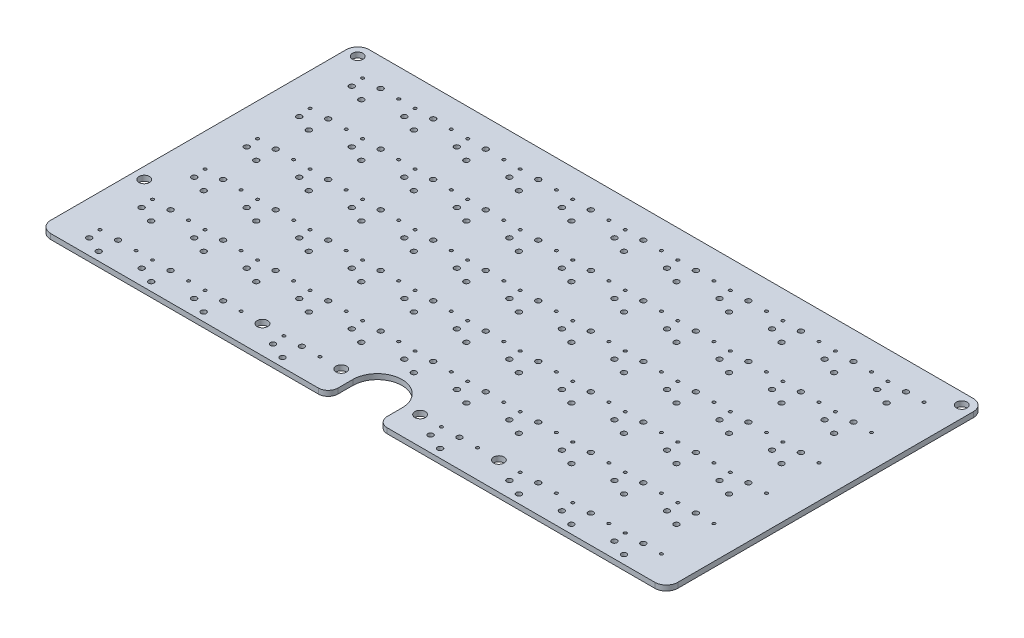
SolidWorks part; units mm, degrees
ref_plane "前视基准面" through (0, 0, 0) normal (0, 0, 1) x (1, 0, 0)
ref_plane "上视基准面" through (0, 0, 0) normal (0, 1, 0) x (1, 0, 0)
ref_plane "右视基准面" through (0, 0, 0) normal (1, 0, 0) x (0, 0, -1)
other "Configuration Table"
sketch "草图1" plane through (0, 0, 0) normal (0, 1, 0) x (1, 0, 0)
  line L0 (187.5, 94.5) -> (187.5, 99)
  line L1 (172.5, 94.5) -> (172.5, 99)
  line L2 (88, 91.5) -> (169.5, 91.5)
  line L3 (190.5, 91.5) -> (272, 91.5)
  line L4 (275.5, 95) -> (275.5, 185)
  line L5 (268.5, 188.5) -> (272, 188.5)
  line L6 (84.5, 185) -> (84.5, 95)
  line L7 (88, 188.5) -> (268.5, 188.5)
  circle A0 centre (187.5, 94.5) radius 0.05
  circle A1 centre (187.5, 99) radius 0.05
  circle A2 centre (172.5, 94.5) radius 0.05
  circle A3 centre (172.5, 99) radius 0.05
  circle A4 centre (88, 91.5) radius 0.05
  circle A5 centre (169.5, 91.5) radius 0.05
  circle A6 centre (190.5, 91.5) radius 0.05
  circle A7 centre (272, 91.5) radius 0.05
  circle A8 centre (275.5, 95) radius 0.05
  circle A9 centre (275.5, 185) radius 0.05
  circle A10 centre (268.5, 188.5) radius 0.05
  circle A11 centre (272, 188.5) radius 0.05
  circle A12 centre (84.5, 185) radius 0.05
  circle A13 centre (84.5, 95) radius 0.05
  circle A14 centre (88, 188.5) radius 0.05
  circle A15 centre (268.5, 188.5) radius 0.05
  arc A16 (180, 106.5) -> (172.5, 99) centre (180, 99) ccw
  circle A17 centre (172.5, 99) radius 0.05
  circle A18 centre (180, 106.5) radius 0.05
  arc A19 (187.5, 99) -> (180, 106.5) centre (180, 99) ccw
  circle A20 centre (180, 106.5) radius 0.05
  circle A21 centre (187.5, 99) radius 0.05
  arc A22 (187.5, 94.5) -> (190.5, 91.5) centre (190.5, 94.5) ccw
  circle A23 centre (190.5, 91.5) radius 0.05
  circle A24 centre (187.5, 94.5) radius 0.05
  arc A25 (169.5, 91.5) -> (172.5, 94.5) centre (169.5, 94.5) ccw
  circle A26 centre (172.5, 94.5) radius 0.05
  circle A27 centre (169.5, 91.5) radius 0.05
  arc A28 (272, 91.5) -> (275.5, 95) centre (272, 95) ccw
  circle A29 centre (275.5, 95) radius 0.05
  circle A30 centre (272, 91.5) radius 0.05
  arc A31 (275.5, 185) -> (272, 188.5) centre (272, 185) ccw
  circle A32 centre (272, 188.5) radius 0.05
  circle A33 centre (275.5, 185) radius 0.05
  arc A34 (88, 188.5) -> (84.5, 185) centre (88, 185) ccw
  circle A35 centre (84.5, 185) radius 0.05
  circle A36 centre (88, 188.5) radius 0.05
  arc A37 (84.5, 95) -> (88, 91.5) centre (88, 95) ccw
  circle A38 centre (88, 91.5) radius 0.05
  circle A39 centre (84.5, 95) radius 0.05
  circle A40 centre (246.6, 136.906) radius 0.1778
  circle A41 centre (170.8, 120.0531) radius 0.1778
  circle A42 centre (177.292, 121.92) radius 0.1778
  circle A43 centre (182.245, 121.666) radius 0.1778
  circle A44 centre (182.245, 119.866) radius 0.1778
  circle A45 centre (268.224, 96.797) radius 0.1778
  circle A46 centre (102.235, 106.1238) radius 0.1778
  circle A47 centre (116.905, 107.315) radius 0.1778
  circle A48 centre (132.905, 107.315) radius 0.1778
  circle A49 centre (156.845, 107.315) radius 0.1778
  circle A50 centre (97.536, 104.284) radius 0.1778
  circle A51 centre (113.5301, 104.284) radius 0.1778
  circle A52 centre (113.5301, 106.1238) radius 0.1778
  circle A53 centre (129.286, 104.284) radius 0.1778
  circle A54 centre (129.286, 106.1238) radius 0.1778
  circle A55 centre (153.5, 104.284) radius 0.1778
  circle A56 centre (153.5, 106.1238) radius 0.1778
  circle A57 centre (198.5, 106.2984) radius 0.1778
  circle A58 centre (225.679, 103.505) radius 0.1778
  circle A59 centre (201.5, 104.26) radius 0.1778
  circle A60 centre (241.5891, 103.759) radius 0.1778
  circle A61 centre (230, 106.6286) radius 0.1778
  circle A62 centre (206, 106.553) radius 0.1778
  circle A63 centre (246.1774, 106.6286) radius 0.1778
  circle A64 centre (260.731, 106.6286) radius 0.1778
  circle A65 centre (264.922, 102.87) radius 0.1778
  circle A66 centre (266.1079, 106.3419) radius 0.1778
  circle A67 centre (264.922, 108.077) radius 0.1778
  circle A68 centre (263.144, 108.077) radius 0.1778
  circle A69 centre (265.2682, 112.9682) radius 0.1778
  circle A70 centre (102.2, 119.42) radius 0.1778
  circle A71 centre (102.2, 121.316) radius 0.1778
  circle A72 centre (118.237, 119.42) radius 0.1778
  circle A73 centre (118.2, 121.316) radius 0.1778
  circle A74 centre (134.239, 119.42) radius 0.1778
  circle A75 centre (134.2, 121.316) radius 0.1778
  circle A76 centre (150.241, 119.42) radius 0.1778
  circle A77 centre (150.2, 121.316) radius 0.1778
  circle A78 centre (166.243, 119.42) radius 0.1778
  circle A79 centre (166.2, 121.316) radius 0.1778
  circle A80 centre (198.2, 119.42) radius 0.1778
  circle A81 centre (198.2, 121.316) radius 0.1778
  circle A82 centre (230.2, 119.42) radius 0.1778
  circle A83 centre (214.2, 119.42) radius 0.1778
  circle A84 centre (214.2, 121.316) radius 0.1778
  circle A85 centre (246.253, 119.6866) radius 0.1778
  circle A86 centre (246.2, 121.316) radius 0.1778
  circle A87 centre (230.2, 121.316) radius 0.1778
  circle A88 centre (262.2, 121.316) radius 0.1778
  circle A89 centre (99.969, 123.038) radius 0.1778
  circle A90 centre (115.969, 123.038) radius 0.1778
  circle A91 centre (131.969, 123.038) radius 0.1778
  circle A92 centre (147.969, 123.038) radius 0.1778
  circle A93 centre (163.969, 123.038) radius 0.1778
  circle A94 centre (179.969, 123.038) radius 0.1778
  circle A95 centre (195.969, 123.038) radius 0.1778
  circle A96 centre (211.969, 123.038) radius 0.1778
  circle A97 centre (227.969, 123.038) radius 0.1778
  circle A98 centre (243.969, 123.038) radius 0.1778
  circle A99 centre (259.969, 123.063) radius 0.1778
  circle A100 centre (257.429, 121.257) radius 0.1778
  circle A101 centre (241.5301, 121.257) radius 0.1778
  circle A102 centre (225.552, 121.316) radius 0.1778
  circle A103 centre (209.5, 121.316) radius 0.1778
  circle A104 centre (193.548, 121.285) radius 0.1778
  circle A105 centre (161.671, 121.316) radius 0.1778
  circle A106 centre (263.6404, 117.729) radius 0.1778
  circle A107 centre (257.6314, 118.618) radius 0.1778
  circle A108 centre (266.5897, 123.063) radius 0.1778
  circle A109 centre (231.6404, 124.46) radius 0.1778
  circle A110 centre (257.6314, 136.284) radius 0.1778
  circle A111 centre (257.556, 138.176) radius 0.1778
  circle A112 centre (241.5301, 137.922) radius 0.1778
  circle A113 centre (241.554, 136.144) radius 0.1778
  circle A114 centre (225.298, 136.284) radius 0.1778
  circle A115 centre (225.298, 138.2141) radius 0.1778
  circle A116 centre (209.55, 136.249) radius 0.1778
  circle A117 centre (209.55, 138.049) radius 0.1778
  circle A118 centre (195.126, 134.874) radius 0.1778
  circle A119 centre (179.126, 134.874) radius 0.1778
  circle A120 centre (163.126, 134.874) radius 0.1778
  circle A121 centre (147.126, 134.874) radius 0.1778
  circle A122 centre (131.126, 134.874) radius 0.1778
  circle A123 centre (115.126, 134.874) radius 0.1778
  circle A124 centre (99.126, 134.874) radius 0.1778
  circle A125 centre (116.956, 139.192) radius 0.1778
  circle A126 centre (132.956, 139.192) radius 0.1778
  circle A127 centre (148.956, 139.192) radius 0.1778
  circle A128 centre (164.956, 139.192) radius 0.1778
  circle A129 centre (180.956, 139.192) radius 0.1778
  circle A130 centre (196.956, 139.192) radius 0.1778
  circle A131 centre (212.956, 139.192) radius 0.1778
  circle A132 centre (228.956, 139.192) radius 0.1778
  circle A133 centre (244.956, 139.192) radius 0.1778
  circle A134 centre (260.956, 139.192) radius 0.1778
  circle A135 centre (100.965, 139.192) radius 0.1778
  circle A136 centre (268.478, 138.938) radius 0.1778
  circle A137 centre (268.5, 155.067) radius 0.1778
  circle A138 centre (182.247, 152.216) radius 0.1778
  circle A139 centre (166.247, 152.216) radius 0.1778
  circle A140 centre (150.247, 152.216) radius 0.1778
  circle A141 centre (134.247, 152.216) radius 0.1778
  circle A142 centre (118.2165, 152.216) radius 0.1778
  circle A143 centre (102.247, 152.216) radius 0.1778
  circle A144 centre (102.247, 154.0137) radius 0.1778
  circle A145 centre (118.247, 154.0137) radius 0.1778
  circle A146 centre (134.247, 154.0137) radius 0.1778
  circle A147 centre (150.247, 154.0137) radius 0.1778
  circle A148 centre (166.247, 154.0137) radius 0.1778
  circle A149 centre (182.247, 154.0137) radius 0.1778
  circle A150 centre (198.247, 154.0137) radius 0.1778
  circle A151 centre (214.249, 154.0137) radius 0.1778
  circle A152 centre (230.194, 154.0137) radius 0.1778
  circle A153 centre (246.253, 154.0137) radius 0.1778
  circle A154 centre (230.251, 152.273) radius 0.1778
  circle A155 centre (198.247, 152.273) radius 0.1778
  circle A156 centre (193.576, 153.278) radius 0.1778
  circle A157 centre (177.576, 153.278) radius 0.1778
  circle A158 centre (116, 155.067) radius 0.1778
  circle A159 centre (132, 155.067) radius 0.1778
  circle A160 centre (148, 155.067) radius 0.1778
  circle A161 centre (164, 155.067) radius 0.1778
  circle A162 centre (180, 155.067) radius 0.1778
  circle A163 centre (196, 155.067) radius 0.1778
  circle A164 centre (212, 155.067) radius 0.1778
  circle A165 centre (228, 155.067) radius 0.1778
  circle A166 centre (244, 155.067) radius 0.1778
  circle A167 centre (257.5301, 154.051) radius 0.1778
  circle A168 centre (260, 155.067) radius 0.1778
  circle A169 centre (102, 170.942) radius 0.1778
  circle A170 centre (102.362, 168.284) radius 0.1778
  circle A171 centre (97.542, 168.402) radius 0.1778
  circle A172 centre (113.542, 168.402) radius 0.1778
  circle A173 centre (113.411, 169.926) radius 0.1778
  circle A174 centre (129.542, 168.402) radius 0.1778
  circle A175 centre (129.54, 169.926) radius 0.1778
  circle A176 centre (118.2165, 168.284) radius 0.1778
  circle A177 centre (150.241, 168.402) radius 0.1778
  circle A178 centre (134.239, 168.284) radius 0.1778
  circle A179 centre (145.542, 168.402) radius 0.1778
  circle A180 centre (145.5301, 169.926) radius 0.1778
  circle A181 centre (161.417, 168.402) radius 0.1778
  circle A182 centre (161.417, 169.926) radius 0.1778
  circle A183 centre (166.243, 168.2844) radius 0.1778
  circle A184 centre (177.546, 168.402) radius 0.1778
  circle A185 centre (177.5301, 169.926) radius 0.1778
  circle A186 centre (182.245, 168.284) radius 0.1778
  circle A187 centre (193.548, 168.284) radius 0.1778
  circle A188 centre (193.548, 169.926) radius 0.1778
  circle A189 centre (198.247, 168.284) radius 0.1778
  circle A190 centre (209.55, 168.284) radius 0.1778
  circle A191 centre (209.5301, 169.926) radius 0.1778
  circle A192 centre (214.249, 168.284) radius 0.1778
  circle A193 centre (230.251, 168.284) radius 0.1778
  circle A194 centre (225.576, 168.3344) radius 0.1778
  circle A195 centre (225.552, 169.926) radius 0.1778
  circle A196 centre (241.554, 168.3344) radius 0.1778
  circle A197 centre (241.5301, 169.926) radius 0.1778
  circle A198 centre (246.253, 168.284) radius 0.1778
  circle A199 centre (257.5301, 168.284) radius 0.1778
  circle A200 centre (257.5301, 169.926) radius 0.1778
  circle A201 centre (262.255, 153.416) radius 0.1778
  circle A202 centre (99.06, 150.876) radius 0.1778
  circle A203 centre (247.637, 156.337) radius 0.1778
  circle A204 centre (254.762, 172.974) radius 0.1778
  circle A205 centre (102.362, 184.873) radius 0.1778
  circle A206 centre (100.9291, 182.8787) radius 0.1778
  circle A207 centre (118.4302, 184.873) radius 0.1778
  circle A208 centre (116.967, 182.8787) radius 0.1778
  circle A209 centre (134.239, 184.873) radius 0.1778
  circle A210 centre (132.969, 182.88) radius 0.1778
  circle A211 centre (150.241, 184.873) radius 0.1778
  circle A212 centre (148.905, 182.88) radius 0.1778
  circle A213 centre (166.37, 184.873) radius 0.1778
  circle A214 centre (164.895, 182.88) radius 0.1778
  circle A215 centre (182.372, 184.912) radius 0.1778
  circle A216 centre (180.975, 182.88) radius 0.1778
  circle A217 centre (198.374, 184.873) radius 0.1778
  circle A218 centre (196.925, 182.88) radius 0.1778
  circle A219 centre (214.376, 184.873) radius 0.1778
  circle A220 centre (212.979, 182.88) radius 0.1778
  circle A221 centre (230.251, 184.873) radius 0.1778
  circle A222 centre (246.253, 184.873) radius 0.1778
  circle A223 centre (262.382, 184.873) radius 0.1778
  circle A224 centre (244.983, 182.88) radius 0.1778
  circle A225 centre (228.925, 182.9495) radius 0.1778
  circle A226 centre (256.929, 183.428) radius 0.1778
  circle A227 centre (240.927, 183.42) radius 0.1778
  circle A228 centre (224.925, 183.428) radius 0.1778
  circle A229 centre (208.923, 183.428) radius 0.1778
  circle A230 centre (192.921, 183.428) radius 0.1778
  circle A231 centre (176.919, 183.428) radius 0.1778
  circle A232 centre (160.917, 183.428) radius 0.1778
  circle A233 centre (144.915, 183.42) radius 0.1778
  circle A234 centre (128.667, 183.428) radius 0.1778
  circle A235 centre (112.649, 183.428) radius 0.1778
  circle A236 centre (96.393, 185) radius 0.1778
  circle A237 centre (99.072, 182.8787) radius 0.1778
  circle A238 centre (115.095, 182.935) radius 0.1778
  circle A239 centre (131.075, 182.925) radius 0.1778
  circle A240 centre (147.185, 182.88) radius 0.1778
  circle A241 centre (163.068, 182.88) radius 0.1778
  circle A242 centre (179.07, 182.88) radius 0.1778
  circle A243 centre (195.072, 182.938) radius 0.1778
  circle A244 centre (211.095, 182.938) radius 0.1778
  circle A245 centre (227.072, 182.938) radius 0.1778
  circle A246 centre (243.072, 182.938) radius 0.1778
  circle A247 centre (259.185, 182.938) radius 0.1778
  circle A248 centre (164.895, 170.942) radius 0.1778
  circle A249 centre (148.905, 170.942) radius 0.1778
  circle A250 centre (196.885, 170.942) radius 0.1778
  circle A251 centre (212.885, 170.942) radius 0.1778
  circle A252 centre (228.885, 170.942) radius 0.1778
  circle A253 centre (244.885, 170.942) radius 0.1778
  circle A254 centre (260.885, 170.942) radius 0.1778
  circle A255 centre (268.478, 170.942) radius 0.1778
  circle A256 centre (180.885, 170.942) radius 0.1778
  circle A257 centre (132.885, 170.942) radius 0.1778
  circle A258 centre (116.885, 170.942) radius 0.1778
  circle A259 centre (271.018, 166.37) radius 0.1778
  circle A260 centre (170.561, 167.767) radius 0.1778
  circle A261 centre (106.8, 185.666) radius 0.1778
  circle A262 centre (122.8, 185.666) radius 0.1778
  circle A263 centre (255.524, 182) radius 0.1778
  circle A264 centre (249.5, 107.8945) radius 0.1778
  circle A265 centre (257.556, 104.297) radius 0.1778
  circle A266 centre (272.415, 95.377) radius 0.1778
  circle A267 centre (271.4106, 97.1434) radius 0.1778
  circle A268 centre (271.018, 107.696) radius 0.1778
  circle A269 centre (270.2444, 180.2014) radius 0.1778
  circle A270 centre (273.558, 180.213) radius 0.1778
  circle A271 centre (268.224, 100.076) radius 0.1778
  circle A272 centre (254.5, 104.297) radius 0.1778
  circle A273 centre (270.002, 100) radius 0.1778
  circle A274 centre (236.093, 104.284) radius 0.1778
  circle A275 centre (252.1274, 104.284) radius 0.1778
  circle A276 centre (262.2, 104.284) radius 0.1778
  circle A277 centre (236.347, 142.113) radius 0.1778
  circle A278 centre (257.556, 185.293) radius 0.1778
  circle A279 centre (241.554, 185.293) radius 0.1778
  circle A280 centre (225.552, 185.293) radius 0.1778
  circle A281 centre (209.55, 185.293) radius 0.1778
  circle A282 centre (193.548, 185.293) radius 0.1778
  circle A283 centre (177.576, 185.316) radius 0.1778
  circle A284 centre (161.671, 185.316) radius 0.1778
  circle A285 centre (145.63, 185.316) radius 0.1778
  circle A286 centre (129.54, 185.316) radius 0.1778
  circle A287 centre (113.411, 185.293) radius 0.1778
  circle A288 centre (246.253, 152.273) radius 0.1778
  circle A289 centre (241.554, 153.316) radius 0.1778
  circle A290 centre (225.552, 153.316) radius 0.1778
  circle A291 centre (214.249, 152.273) radius 0.1778
  circle A292 centre (209.55, 153.316) radius 0.1778
  circle A293 centre (161.671, 153.316) radius 0.1778
  circle A294 centre (145.63, 153.316) radius 0.1778
  circle A295 centre (129.54, 153.316) radius 0.1778
  circle A296 centre (113.665, 153.316) radius 0.1778
  circle A297 centre (102.489, 136.271) radius 0.1778
  circle A298 centre (113.665, 137.414) radius 0.1778
  circle A299 centre (118.237, 136.284) radius 0.1778
  circle A300 centre (129.54, 137.414) radius 0.1778
  circle A301 centre (134.239, 136.284) radius 0.1778
  circle A302 centre (145.6, 137.414) radius 0.1778
  circle A303 centre (150.241, 136.284) radius 0.1778
  circle A304 centre (161.671, 137.384) radius 0.1778
  circle A305 centre (166.243, 136.284) radius 0.1778
  circle A306 centre (177.546, 137.414) radius 0.1778
  circle A307 centre (182.245, 136.284) radius 0.1778
  circle A308 centre (193.802, 137.414) radius 0.1778
  circle A309 centre (198.447, 136.284) radius 0.1778
  circle A310 centre (214.249, 136.284) radius 0.1778
  circle A311 centre (230.505, 136.284) radius 0.1778
  circle A312 centre (145.6, 121.316) radius 0.1778
  circle A313 centre (129.54, 121.316) radius 0.1778
  circle A314 centre (113.665, 121.316) radius 0.1778
  circle A315 centre (102.235, 104.26) radius 0.1778
  circle A316 centre (118.237, 104.26) radius 0.1778
  circle A317 centre (146.818, 103.505) radius 0.1778
  circle A318 centre (134.239, 104.284) radius 0.1778
  circle A319 centre (218.8, 103.251) radius 0.1778
  circle A320 centre (225.552, 105.384) radius 0.1778
  circle A321 centre (206, 104.26) radius 0.1778
  circle A322 centre (241.554, 105.384) radius 0.1778
  circle A323 centre (230, 104.26) radius 0.1778
  circle A324 centre (246.253, 104.26) radius 0.1778
  circle A325 centre (250.8, 119.42) radius 0.1778
  circle A326 centre (250.8, 135.42) radius 0.1778
  circle A327 centre (250.8, 151.42) radius 0.1778
  circle A328 centre (250.8, 167.42) radius 0.1778
  circle A329 centre (250.8, 183.428) radius 0.1778
  circle A330 centre (234.8, 119.42) radius 0.1778
  circle A331 centre (234.8, 135.42) radius 0.1778
  circle A332 centre (234.8, 151.42) radius 0.1778
  circle A333 centre (234.8, 167.42) radius 0.1778
  circle A334 centre (234.8, 183.428) radius 0.1778
  circle A335 centre (218.8, 119.42) radius 0.1778
  circle A336 centre (218.8, 135.42) radius 0.1778
  circle A337 centre (218.8, 151.42) radius 0.1778
  circle A338 centre (218.8, 167.42) radius 0.1778
  circle A339 centre (218.8, 183.428) radius 0.1778
  circle A340 centre (202.8, 119.42) radius 0.1778
  circle A341 centre (202.8, 135.42) radius 0.1778
  circle A342 centre (202.8, 151.42) radius 0.1778
  circle A343 centre (202.8, 167.42) radius 0.1778
  circle A344 centre (202.8, 183.428) radius 0.1778
  circle A345 centre (186.8, 119.42) radius 0.1778
  circle A346 centre (186.8, 135.42) radius 0.1778
  circle A347 centre (186.8, 151.42) radius 0.1778
  circle A348 centre (186.8, 167.42) radius 0.1778
  circle A349 centre (186.8, 183.428) radius 0.1778
  circle A350 centre (170.8, 135.42) radius 0.1778
  circle A351 centre (170.8, 151.42) radius 0.1778
  circle A352 centre (170.561, 183.428) radius 0.1778
  circle A353 centre (154.8, 119.42) radius 0.1778
  circle A354 centre (154.8, 135.42) radius 0.1778
  circle A355 centre (154.8, 151.42) radius 0.1778
  circle A356 centre (154.8, 167.42) radius 0.1778
  circle A357 centre (154.8, 183.428) radius 0.1778
  circle A358 centre (138.8, 119.42) radius 0.1778
  circle A359 centre (138.8, 135.42) radius 0.1778
  circle A360 centre (138.8, 151.42) radius 0.1778
  circle A361 centre (138.8, 167.42) radius 0.1778
  circle A362 centre (138.8, 183.428) radius 0.1778
  circle A363 centre (122.8, 102.42) radius 0.1778
  circle A364 centre (122.8, 119.42) radius 0.1778
  circle A365 centre (122.8, 135.42) radius 0.1778
  circle A366 centre (122.8, 151.42) radius 0.1778
  circle A367 centre (122.8, 167.42) radius 0.1778
  circle A368 centre (122.8, 183.428) radius 0.1778
  circle A369 centre (106.8, 102.512) radius 0.1778
  circle A370 centre (106.8, 119.42) radius 0.1778
  circle A371 centre (106.8, 135.42) radius 0.1778
  circle A372 centre (106.8, 151.42) radius 0.1778
  circle A373 centre (106.8, 167.42) radius 0.1778
  circle A374 centre (106.8, 183.428) radius 0.1778
  circle A375 centre (93.472, 183.428) radius 0.1778
  circle A376 centre (92.075, 168.91) radius 0.1778
  circle A377 centre (92.075, 153.035) radius 0.1778
  circle A378 centre (92.075, 136.906) radius 0.1778
  circle A379 centre (88, 120) radius 0.8
  circle A380 centre (216, 100) radius 0.8
  circle A381 centre (144, 100) radius 0.8
  circle A382 centre (192, 100) radius 0.8
  circle A383 centre (168, 100) radius 0.8
  circle A384 centre (272, 185) radius 0.8
  circle A385 centre (88, 185) radius 0.8
  circle A386 centre (239, 176.2) radius 0.8
  circle A387 centre (244, 174.1) radius 0.8
  circle A388 centre (244, 180) radius 0.8
  circle A389 centre (249.5, 180) radius 0.45
  circle A390 centre (238.5, 180) radius 0.45
  circle A391 centre (222.5, 180) radius 0.45
  circle A392 centre (233.5, 180) radius 0.45
  circle A393 centre (228, 180) radius 0.8
  circle A394 centre (228, 174.1) radius 0.8
  circle A395 centre (223, 176.2) radius 0.8
  circle A396 centre (207, 176.2) radius 0.8
  circle A397 centre (212, 174.1) radius 0.8
  circle A398 centre (212, 180) radius 0.8
  circle A399 centre (217.5, 180) radius 0.45
  circle A400 centre (206.5, 180) radius 0.45
  circle A401 centre (190.5, 180) radius 0.45
  circle A402 centre (201.5, 180) radius 0.45
  circle A403 centre (196, 180) radius 0.8
  circle A404 centre (196, 174.1) radius 0.8
  circle A405 centre (191, 176.2) radius 0.8
  circle A406 centre (175, 176.2) radius 0.8
  circle A407 centre (180, 174.1) radius 0.8
  circle A408 centre (180, 180) radius 0.8
  circle A409 centre (185.5, 180) radius 0.45
  circle A410 centre (174.5, 180) radius 0.45
  circle A411 centre (158.5, 180) radius 0.45
  circle A412 centre (169.5, 180) radius 0.45
  circle A413 centre (164, 180) radius 0.8
  circle A414 centre (164, 174.1) radius 0.8
  circle A415 centre (159, 176.2) radius 0.8
  circle A416 centre (143, 176.2) radius 0.8
  circle A417 centre (148, 174.1) radius 0.8
  circle A418 centre (148, 180) radius 0.8
  circle A419 centre (153.5, 180) radius 0.45
  circle A420 centre (142.5, 180) radius 0.45
  circle A421 centre (126.5, 180) radius 0.45
  circle A422 centre (137.5, 180) radius 0.45
  circle A423 centre (132, 180) radius 0.8
  circle A424 centre (132, 174.1) radius 0.8
  circle A425 centre (127, 176.2) radius 0.8
  circle A426 centre (111, 176.2) radius 0.8
  circle A427 centre (116, 174.1) radius 0.8
  circle A428 centre (116, 180) radius 0.8
  circle A429 centre (121.5, 180) radius 0.45
  circle A430 centre (110.5, 180) radius 0.45
  circle A431 centre (94.5, 180) radius 0.45
  circle A432 centre (105.5, 180) radius 0.45
  circle A433 centre (100, 180) radius 0.8
  circle A434 centre (100, 174.1) radius 0.8
  circle A435 centre (95, 176.2) radius 0.8
  circle A436 centre (239, 160.2) radius 0.8
  circle A437 centre (244, 158.1) radius 0.8
  circle A438 centre (244, 164) radius 0.8
  circle A439 centre (249.5, 164) radius 0.45
  circle A440 centre (238.5, 164) radius 0.45
  circle A441 centre (222.5, 164) radius 0.45
  circle A442 centre (233.5, 164) radius 0.45
  circle A443 centre (228, 164) radius 0.8
  circle A444 centre (228, 158.1) radius 0.8
  circle A445 centre (223, 160.2) radius 0.8
  circle A446 centre (207, 160.2) radius 0.8
  circle A447 centre (212, 158.1) radius 0.8
  circle A448 centre (212, 164) radius 0.8
  circle A449 centre (217.5, 164) radius 0.45
  circle A450 centre (206.5, 164) radius 0.45
  circle A451 centre (190.5, 164) radius 0.45
  circle A452 centre (201.5, 164) radius 0.45
  circle A453 centre (196, 164) radius 0.8
  circle A454 centre (196, 158.1) radius 0.8
  circle A455 centre (191, 160.2) radius 0.8
  circle A456 centre (175, 160.2) radius 0.8
  circle A457 centre (180, 158.1) radius 0.8
  circle A458 centre (180, 164) radius 0.8
  circle A459 centre (185.5, 164) radius 0.45
  circle A460 centre (174.5, 164) radius 0.45
  circle A461 centre (158.5, 164) radius 0.45
  circle A462 centre (169.5, 164) radius 0.45
  circle A463 centre (164, 164) radius 0.8
  circle A464 centre (164, 158.1) radius 0.8
  circle A465 centre (159, 160.2) radius 0.8
  circle A466 centre (143, 160.2) radius 0.8
  circle A467 centre (148, 158.1) radius 0.8
  circle A468 centre (148, 164) radius 0.8
  circle A469 centre (153.5, 164) radius 0.45
  circle A470 centre (142.5, 164) radius 0.45
  circle A471 centre (126.5, 164) radius 0.45
  circle A472 centre (137.5, 164) radius 0.45
  circle A473 centre (132, 164) radius 0.8
  circle A474 centre (132, 158.1) radius 0.8
  circle A475 centre (127, 160.2) radius 0.8
  circle A476 centre (111, 160.2) radius 0.8
  circle A477 centre (116, 158.1) radius 0.8
  circle A478 centre (116, 164) radius 0.8
  circle A479 centre (121.5, 164) radius 0.45
  circle A480 centre (110.5, 164) radius 0.45
  circle A481 centre (94.5, 164) radius 0.45
  circle A482 centre (105.5, 164) radius 0.45
  circle A483 centre (100, 164) radius 0.8
  circle A484 centre (100, 158.1) radius 0.8
  circle A485 centre (95, 160.2) radius 0.8
  circle A486 centre (239, 144.2) radius 0.8
  circle A487 centre (244, 142.1) radius 0.8
  circle A488 centre (244, 148) radius 0.8
  circle A489 centre (249.5, 148) radius 0.45
  circle A490 centre (238.5, 148) radius 0.45
  circle A491 centre (222.5, 148) radius 0.45
  circle A492 centre (233.5, 148) radius 0.45
  circle A493 centre (228, 148) radius 0.8
  circle A494 centre (228, 142.1) radius 0.8
  circle A495 centre (223, 144.2) radius 0.8
  circle A496 centre (207, 144.2) radius 0.8
  circle A497 centre (212, 142.1) radius 0.8
  circle A498 centre (212, 148) radius 0.8
  circle A499 centre (217.5, 148) radius 0.45
  circle A500 centre (206.5, 148) radius 0.45
  circle A501 centre (190.5, 148) radius 0.45
  circle A502 centre (201.5, 148) radius 0.45
  circle A503 centre (196, 148) radius 0.8
  circle A504 centre (196, 142.1) radius 0.8
  circle A505 centre (191, 144.2) radius 0.8
  circle A506 centre (175, 144.2) radius 0.8
  circle A507 centre (180, 142.1) radius 0.8
  circle A508 centre (180, 148) radius 0.8
  circle A509 centre (185.5, 148) radius 0.45
  circle A510 centre (174.5, 148) radius 0.45
  circle A511 centre (158.5, 148) radius 0.45
  circle A512 centre (169.5, 148) radius 0.45
  circle A513 centre (164, 148) radius 0.8
  circle A514 centre (164, 142.1) radius 0.8
  circle A515 centre (159, 144.2) radius 0.8
  circle A516 centre (143, 144.2) radius 0.8
  circle A517 centre (148, 142.1) radius 0.8
  circle A518 centre (148, 148) radius 0.8
  circle A519 centre (153.5, 148) radius 0.45
  circle A520 centre (142.5, 148) radius 0.45
  circle A521 centre (126.5, 148) radius 0.45
  circle A522 centre (137.5, 148) radius 0.45
  circle A523 centre (132, 148) radius 0.8
  circle A524 centre (132, 142.1) radius 0.8
  circle A525 centre (127, 144.2) radius 0.8
  circle A526 centre (111, 144.2) radius 0.8
  circle A527 centre (116, 142.1) radius 0.8
  circle A528 centre (116, 148) radius 0.8
  circle A529 centre (121.5, 148) radius 0.45
  circle A530 centre (110.5, 148) radius 0.45
  circle A531 centre (94.5, 148) radius 0.45
  circle A532 centre (105.5, 148) radius 0.45
  circle A533 centre (100, 148) radius 0.8
  circle A534 centre (100, 142.1) radius 0.8
  circle A535 centre (95, 144.2) radius 0.8
  circle A536 centre (239, 128.2) radius 0.8
  circle A537 centre (244, 126.1) radius 0.8
  circle A538 centre (244, 132) radius 0.8
  circle A539 centre (249.5, 132) radius 0.45
  circle A540 centre (238.5, 132) radius 0.45
  circle A541 centre (222.5, 132) radius 0.45
  circle A542 centre (233.5, 132) radius 0.45
  circle A543 centre (228, 132) radius 0.8
  circle A544 centre (228, 126.1) radius 0.8
  circle A545 centre (223, 128.2) radius 0.8
  circle A546 centre (207, 128.2) radius 0.8
  circle A547 centre (212, 126.1) radius 0.8
  circle A548 centre (212, 132) radius 0.8
  circle A549 centre (217.5, 132) radius 0.45
  circle A550 centre (206.5, 132) radius 0.45
  circle A551 centre (190.5, 132) radius 0.45
  circle A552 centre (201.5, 132) radius 0.45
  circle A553 centre (196, 132) radius 0.8
  circle A554 centre (196, 126.1) radius 0.8
  circle A555 centre (191, 128.2) radius 0.8
  circle A556 centre (175, 128.2) radius 0.8
  circle A557 centre (180, 126.1) radius 0.8
  circle A558 centre (180, 132) radius 0.8
  circle A559 centre (185.5, 132) radius 0.45
  circle A560 centre (174.5, 132) radius 0.45
  circle A561 centre (158.5, 132) radius 0.45
  circle A562 centre (169.5, 132) radius 0.45
  circle A563 centre (164, 132) radius 0.8
  circle A564 centre (164, 126.1) radius 0.8
  circle A565 centre (159, 128.2) radius 0.8
  circle A566 centre (143, 128.2) radius 0.8
  circle A567 centre (148, 126.1) radius 0.8
  circle A568 centre (148, 132) radius 0.8
  circle A569 centre (153.5, 132) radius 0.45
  circle A570 centre (142.5, 132) radius 0.45
  circle A571 centre (126.5, 132) radius 0.45
  circle A572 centre (137.5, 132) radius 0.45
  circle A573 centre (132, 132) radius 0.8
  circle A574 centre (132, 126.1) radius 0.8
  circle A575 centre (127, 128.2) radius 0.8
  circle A576 centre (111, 128.2) radius 0.8
  circle A577 centre (116, 126.1) radius 0.8
  circle A578 centre (116, 132) radius 0.8
  circle A579 centre (121.5, 132) radius 0.45
  circle A580 centre (110.5, 132) radius 0.45
  circle A581 centre (94.5, 132) radius 0.45
  circle A582 centre (105.5, 132) radius 0.45
  circle A583 centre (100, 132) radius 0.8
  circle A584 centre (100, 126.1) radius 0.8
  circle A585 centre (95, 128.2) radius 0.8
  circle A586 centre (239, 112.2) radius 0.8
  circle A587 centre (244, 110.1) radius 0.8
  circle A588 centre (244, 116) radius 0.8
  circle A589 centre (249.5, 116) radius 0.45
  circle A590 centre (238.5, 116) radius 0.45
  circle A591 centre (222.5, 116) radius 0.45
  circle A592 centre (233.5, 116) radius 0.45
  circle A593 centre (228, 116) radius 0.8
  circle A594 centre (228, 110.1) radius 0.8
  circle A595 centre (223, 112.2) radius 0.8
  circle A596 centre (207, 112.2) radius 0.8
  circle A597 centre (212, 110.1) radius 0.8
  circle A598 centre (212, 116) radius 0.8
  circle A599 centre (217.5, 116) radius 0.45
  circle A600 centre (206.5, 116) radius 0.45
  circle A601 centre (190.5, 116) radius 0.45
  circle A602 centre (201.5, 116) radius 0.45
  circle A603 centre (196, 116) radius 0.8
  circle A604 centre (196, 110.1) radius 0.8
  circle A605 centre (191, 112.2) radius 0.8
  circle A606 centre (175, 112.2) radius 0.8
  circle A607 centre (180, 110.1) radius 0.8
  circle A608 centre (180, 116) radius 0.8
  circle A609 centre (185.5, 116) radius 0.45
  circle A610 centre (174.5, 116) radius 0.45
  circle A611 centre (158.5, 116) radius 0.45
  circle A612 centre (169.5, 116) radius 0.45
  circle A613 centre (164, 116) radius 0.8
  circle A614 centre (164, 110.1) radius 0.8
  circle A615 centre (159, 112.2) radius 0.8
  circle A616 centre (143, 112.2) radius 0.8
  circle A617 centre (148, 110.1) radius 0.8
  circle A618 centre (148, 116) radius 0.8
  circle A619 centre (153.5, 116) radius 0.45
  circle A620 centre (142.5, 116) radius 0.45
  circle A621 centre (126.5, 116) radius 0.45
  circle A622 centre (137.5, 116) radius 0.45
  circle A623 centre (132, 116) radius 0.8
  circle A624 centre (132, 110.1) radius 0.8
  circle A625 centre (127, 112.2) radius 0.8
  circle A626 centre (111, 112.2) radius 0.8
  circle A627 centre (116, 110.1) radius 0.8
  circle A628 centre (116, 116) radius 0.8
  circle A629 centre (121.5, 116) radius 0.45
  circle A630 centre (110.5, 116) radius 0.45
  circle A631 centre (94.5, 116) radius 0.45
  circle A632 centre (105.5, 116) radius 0.45
  circle A633 centre (100, 116) radius 0.8
  circle A634 centre (100, 110.1) radius 0.8
  circle A635 centre (95, 112.2) radius 0.8
  circle A636 centre (239, 96.2) radius 0.8
  circle A637 centre (244, 94.1) radius 0.8
  circle A638 centre (244, 100) radius 0.8
  circle A639 centre (249.5, 100) radius 0.45
  circle A640 centre (238.5, 100) radius 0.45
  circle A641 centre (222.5, 100) radius 0.45
  circle A642 centre (233.5, 100) radius 0.45
  circle A643 centre (228, 100) radius 0.8
  circle A644 centre (228, 94.1) radius 0.8
  circle A645 centre (223, 96.2) radius 0.8
  circle A646 centre (199, 96.2) radius 0.8
  circle A647 centre (204, 94.1) radius 0.8
  circle A648 centre (204, 100) radius 0.8
  circle A649 centre (209.5, 100) radius 0.45
  circle A650 centre (198.5, 100) radius 0.45
  circle A651 centre (254.5, 180) radius 0.45
  circle A652 centre (265.5, 180) radius 0.45
  circle A653 centre (260, 180) radius 0.8
  circle A654 centre (260, 174.1) radius 0.8
  circle A655 centre (255, 176.2) radius 0.8
  circle A656 centre (255, 160.2) radius 0.8
  circle A657 centre (260, 158.1) radius 0.8
  circle A658 centre (260, 164) radius 0.8
  circle A659 centre (265.5, 164) radius 0.45
  circle A660 centre (254.5, 164) radius 0.45
  circle A661 centre (150.5, 100) radius 0.45
  circle A662 centre (161.5, 100) radius 0.45
  circle A663 centre (156, 100) radius 0.8
  circle A664 centre (156, 94.1) radius 0.8
  circle A665 centre (151, 96.2) radius 0.8
  circle A666 centre (255, 144.2) radius 0.8
  circle A667 centre (260, 142.1) radius 0.8
  circle A668 centre (260, 148) radius 0.8
  circle A669 centre (265.5, 148) radius 0.45
  circle A670 centre (254.5, 148) radius 0.45
  circle A671 centre (126.5, 100) radius 0.45
  circle A672 centre (137.5, 100) radius 0.45
  circle A673 centre (132, 100) radius 0.8
  circle A674 centre (132, 94.1) radius 0.8
  circle A675 centre (127, 96.2) radius 0.8
  circle A676 centre (255, 128.2) radius 0.8
  circle A677 centre (260, 126.1) radius 0.8
  circle A678 centre (260, 132) radius 0.8
  circle A679 centre (265.5, 132) radius 0.45
  circle A680 centre (254.5, 132) radius 0.45
  circle A681 centre (110.5, 100) radius 0.45
  circle A682 centre (121.5, 100) radius 0.45
  circle A683 centre (116, 100) radius 0.8
  circle A684 centre (116, 94.1) radius 0.8
  circle A685 centre (111, 96.2) radius 0.8
  circle A686 centre (255, 112.2) radius 0.8
  circle A687 centre (260, 110.1) radius 0.8
  circle A688 centre (260, 116) radius 0.8
  circle A689 centre (265.5, 116) radius 0.45
  circle A690 centre (254.5, 116) radius 0.45
  circle A691 centre (94.5, 100) radius 0.45
  circle A692 centre (105.5, 100) radius 0.45
  circle A693 centre (100, 100) radius 0.8
  circle A694 centre (100, 94.1) radius 0.8
  circle A695 centre (95, 96.2) radius 0.8
  circle A696 centre (255, 96.2) radius 0.8
  circle A697 centre (260, 94.1) radius 0.8
  circle A698 centre (260, 100) radius 0.8
  circle A699 centre (265.5, 100) radius 0.45
  circle A700 centre (254.5, 100) radius 0.45
sketch "草图2" plane through (0, 0, 0) normal (0, 1, 0) x (1, 0, 0)
  line L8 (187.5, 99) -> (187.5, 94.5)
  line L9 (190.5, 91.5) -> (272, 91.5)
  line L10 (275.5, 95) -> (275.5, 185)
  line L11 (272, 188.5) -> (268.5, 188.5)
  line L12 (268.5, 188.5) -> (88, 188.5)
  line L13 (84.5, 185) -> (84.5, 95)
  line L14 (88, 91.5) -> (169.5, 91.5)
  line L15 (172.5, 94.5) -> (172.5, 99)
  line L16 (187.5, 99) -> (187.5, 94.5)
  line L17 (190.5, 91.5) -> (272, 91.5)
  line L18 (275.5, 95) -> (275.5, 185)
  line L19 (272, 188.5) -> (268.5, 188.5)
  line L20 (268.5, 188.5) -> (88, 188.5)
  line L21 (84.5, 185) -> (84.5, 95)
  line L22 (88, 91.5) -> (169.5, 91.5)
  line L23 (172.5, 94.5) -> (172.5, 99)
  circle A1 centre (260, 94.1) radius 0.8
  circle A2 centre (260, 94.1) radius 0.8
  circle A3 centre (255, 96.2) radius 0.8
  circle A4 centre (255, 96.2) radius 0.8
  circle A5 centre (95, 96.2) radius 0.8
  circle A6 centre (95, 96.2) radius 0.8
  circle A7 centre (100, 94.1) radius 0.8
  circle A8 centre (100, 94.1) radius 0.8
  circle A9 centre (100, 100) radius 0.8
  circle A10 centre (100, 100) radius 0.8
  circle A11 centre (105.5, 100) radius 0.45
  circle A12 centre (105.5, 100) radius 0.45
  circle A13 centre (94.5, 100) radius 0.45
  circle A14 centre (94.5, 100) radius 0.45
  circle A15 centre (254.5, 116) radius 0.45
  circle A16 centre (254.5, 116) radius 0.45
  circle A17 centre (158.5, 132) radius 0.45
  circle A18 centre (158.5, 132) radius 0.45
  circle A19 centre (174.5, 132) radius 0.45
  circle A20 centre (174.5, 132) radius 0.45
  circle A21 centre (185.5, 132) radius 0.45
  circle A22 centre (185.5, 132) radius 0.45
  circle A23 centre (180, 132) radius 0.8
  circle A24 centre (180, 132) radius 0.8
  circle A25 centre (180, 126.1) radius 0.8
  circle A26 centre (180, 126.1) radius 0.8
  circle A27 centre (175, 128.2) radius 0.8
  circle A28 centre (175, 128.2) radius 0.8
  circle A29 centre (191, 128.2) radius 0.8
  circle A30 centre (191, 128.2) radius 0.8
  circle A31 centre (196, 126.1) radius 0.8
  circle A32 centre (196, 126.1) radius 0.8
  circle A33 centre (127, 176.2) radius 0.8
  circle A34 centre (127, 176.2) radius 0.8
  circle A35 centre (132, 174.1) radius 0.8
  circle A36 centre (132, 174.1) radius 0.8
  circle A37 centre (132, 180) radius 0.8
  circle A38 centre (132, 180) radius 0.8
  circle A39 centre (137.5, 180) radius 0.45
  circle A40 centre (137.5, 180) radius 0.45
  circle A41 centre (126.5, 180) radius 0.45
  circle A42 centre (126.5, 180) radius 0.45
  circle A43 centre (142.5, 180) radius 0.45
  circle A44 centre (142.5, 180) radius 0.45
  circle A45 centre (153.5, 180) radius 0.45
  circle A46 centre (153.5, 180) radius 0.45
  circle A47 centre (148, 180) radius 0.8
  circle A48 centre (148, 180) radius 0.8
  circle A93 centre (254.5, 100) radius 0.45
  circle A94 centre (254.5, 100) radius 0.45
  circle A95 centre (265.5, 100) radius 0.45
  circle A96 centre (265.5, 100) radius 0.45
  circle A97 centre (260, 100) radius 0.8
  circle A98 centre (260, 100) radius 0.8
  circle A99 centre (153.5, 132) radius 0.45
  circle A100 centre (153.5, 132) radius 0.45
  circle A101 centre (148, 132) radius 0.8
  circle A102 centre (148, 132) radius 0.8
  circle A103 centre (148, 126.1) radius 0.8
  circle A104 centre (148, 126.1) radius 0.8
  circle A105 centre (143, 128.2) radius 0.8
  circle A106 centre (143, 128.2) radius 0.8
  circle A107 centre (159, 128.2) radius 0.8
  circle A108 centre (159, 128.2) radius 0.8
  circle A109 centre (164, 126.1) radius 0.8
  circle A110 centre (164, 126.1) radius 0.8
  circle A111 centre (164, 132) radius 0.8
  circle A112 centre (164, 132) radius 0.8
  circle A113 centre (169.5, 132) radius 0.45
  circle A114 centre (169.5, 132) radius 0.45
  circle A115 centre (100, 180) radius 0.8
  circle A116 centre (100, 180) radius 0.8
  circle A117 centre (105.5, 180) radius 0.45
  circle A118 centre (105.5, 180) radius 0.45
  circle A119 centre (94.5, 180) radius 0.45
  circle A120 centre (94.5, 180) radius 0.45
  circle A121 centre (110.5, 180) radius 0.45
  circle A122 centre (110.5, 180) radius 0.45
  circle A123 centre (121.5, 180) radius 0.45
  circle A124 centre (121.5, 180) radius 0.45
  circle A125 centre (116, 180) radius 0.8
  circle A126 centre (116, 180) radius 0.8
  circle A127 centre (116, 174.1) radius 0.8
  circle A128 centre (116, 174.1) radius 0.8
  circle A129 centre (111, 176.2) radius 0.8
  circle A130 centre (111, 176.2) radius 0.8
  circle A179 centre (116, 126.1) radius 0.8
  circle A180 centre (116, 126.1) radius 0.8
  circle A181 centre (111, 128.2) radius 0.8
  circle A182 centre (111, 128.2) radius 0.8
  circle A183 centre (127, 128.2) radius 0.8
  circle A184 centre (127, 128.2) radius 0.8
  circle A185 centre (132, 126.1) radius 0.8
  circle A186 centre (132, 126.1) radius 0.8
  circle A187 centre (132, 132) radius 0.8
  circle A188 centre (132, 132) radius 0.8
  circle A189 centre (137.5, 132) radius 0.45
  circle A190 centre (137.5, 132) radius 0.45
  circle A191 centre (126.5, 132) radius 0.45
  circle A192 centre (126.5, 132) radius 0.45
  circle A193 centre (142.5, 132) radius 0.45
  circle A194 centre (142.5, 132) radius 0.45
  circle A195 centre (222.5, 164) radius 0.45
  circle A196 centre (222.5, 164) radius 0.45
  circle A197 centre (238.5, 164) radius 0.45
  circle A198 centre (238.5, 164) radius 0.45
  circle A199 centre (249.5, 164) radius 0.45
  circle A200 centre (249.5, 164) radius 0.45
  circle A201 centre (244, 164) radius 0.8
  circle A202 centre (244, 164) radius 0.8
  circle A203 centre (244, 158.1) radius 0.8
  circle A204 centre (244, 158.1) radius 0.8
  circle A205 centre (239, 160.2) radius 0.8
  circle A206 centre (239, 160.2) radius 0.8
  circle A207 centre (95, 176.2) radius 0.8
  circle A208 centre (95, 176.2) radius 0.8
  circle A209 centre (100, 174.1) radius 0.8
  circle A210 centre (100, 174.1) radius 0.8
  circle A263 centre (95, 128.2) radius 0.8
  circle A264 centre (95, 128.2) radius 0.8
  circle A265 centre (100, 126.1) radius 0.8
  arc A266 (187.5, 99) -> (180, 106.5) centre (180, 99) ccw
  arc A267 (187.5, 94.5) -> (190.5, 91.5) centre (190.5, 94.5) ccw
  arc A268 (272, 91.5) -> (275.5, 95) centre (272, 95) ccw
  arc A269 (275.5, 185) -> (272, 188.5) centre (272, 185) ccw
  arc A270 (88, 188.5) -> (84.5, 185) centre (88, 185) ccw
  arc A271 (84.5, 95) -> (88, 91.5) centre (88, 95) ccw
  arc A272 (169.5, 91.5) -> (172.5, 94.5) centre (169.5, 94.5) ccw
  arc A273 (180, 106.5) -> (172.5, 99) centre (180, 99) ccw
  arc A274 (187.5, 99) -> (180, 106.5) centre (180, 99) ccw
  arc A275 (187.5, 94.5) -> (190.5, 91.5) centre (190.5, 94.5) ccw
  arc A276 (272, 91.5) -> (275.5, 95) centre (272, 95) ccw
  arc A277 (275.5, 185) -> (272, 188.5) centre (272, 185) ccw
  arc A278 (88, 188.5) -> (84.5, 185) centre (88, 185) ccw
  arc A279 (84.5, 95) -> (88, 91.5) centre (88, 95) ccw
  arc A280 (169.5, 91.5) -> (172.5, 94.5) centre (169.5, 94.5) ccw
  arc A281 (180, 106.5) -> (172.5, 99) centre (180, 99) ccw
  circle A282 centre (100, 126.1) radius 0.8
  circle A283 centre (100, 132) radius 0.8
  circle A284 centre (100, 132) radius 0.8
  circle A285 centre (105.5, 132) radius 0.45
  circle A286 centre (105.5, 132) radius 0.45
  circle A287 centre (94.5, 132) radius 0.45
  circle A288 centre (94.5, 132) radius 0.45
  circle A289 centre (110.5, 132) radius 0.45
  circle A290 centre (110.5, 132) radius 0.45
  circle A291 centre (121.5, 132) radius 0.45
  circle A292 centre (121.5, 132) radius 0.45
  circle A293 centre (116, 132) radius 0.8
  circle A294 centre (116, 132) radius 0.8
  circle A295 centre (217.5, 164) radius 0.45
  circle A296 centre (217.5, 164) radius 0.45
  circle A297 centre (212, 164) radius 0.8
  circle A298 centre (212, 164) radius 0.8
  circle A299 centre (212, 158.1) radius 0.8
  circle A300 centre (212, 158.1) radius 0.8
  circle A301 centre (207, 160.2) radius 0.8
  circle A302 centre (207, 160.2) radius 0.8
  circle A303 centre (223, 160.2) radius 0.8
  circle A304 centre (223, 160.2) radius 0.8
  circle A305 centre (228, 158.1) radius 0.8
  circle A306 centre (228, 158.1) radius 0.8
  circle A307 centre (228, 164) radius 0.8
  circle A308 centre (228, 164) radius 0.8
  circle A309 centre (233.5, 164) radius 0.45
  circle A310 centre (233.5, 164) radius 0.45
  circle A361 centre (228, 116) radius 0.8
  circle A362 centre (228, 116) radius 0.8
  circle A363 centre (233.5, 116) radius 0.45
  circle A364 centre (233.5, 116) radius 0.45
  circle A365 centre (222.5, 116) radius 0.45
  circle A366 centre (222.5, 116) radius 0.45
  circle A367 centre (238.5, 116) radius 0.45
  circle A368 centre (238.5, 116) radius 0.45
  circle A369 centre (249.5, 116) radius 0.45
  circle A370 centre (249.5, 116) radius 0.45
  circle A371 centre (244, 116) radius 0.8
  circle A372 centre (244, 116) radius 0.8
  circle A373 centre (244, 110.1) radius 0.8
  circle A374 centre (244, 110.1) radius 0.8
  circle A375 centre (239, 112.2) radius 0.8
  circle A376 centre (239, 112.2) radius 0.8
  circle A377 centre (180, 158.1) radius 0.8
  circle A378 centre (180, 158.1) radius 0.8
  circle A379 centre (175, 160.2) radius 0.8
  circle A380 centre (175, 160.2) radius 0.8
  circle A381 centre (191, 160.2) radius 0.8
  circle A382 centre (191, 160.2) radius 0.8
  circle A383 centre (196, 158.1) radius 0.8
  circle A384 centre (196, 158.1) radius 0.8
  circle A385 centre (196, 164) radius 0.8
  circle A386 centre (196, 164) radius 0.8
  circle A387 centre (201.5, 164) radius 0.45
  circle A388 centre (201.5, 164) radius 0.45
  circle A389 centre (190.5, 164) radius 0.45
  circle A390 centre (190.5, 164) radius 0.45
  circle A391 centre (206.5, 164) radius 0.45
  circle A392 centre (206.5, 164) radius 0.45
  circle A441 centre (190.5, 116) radius 0.45
  circle A442 centre (190.5, 116) radius 0.45
  circle A443 centre (206.5, 116) radius 0.45
  circle A444 centre (206.5, 116) radius 0.45
  circle A445 centre (217.5, 116) radius 0.45
  circle A446 centre (217.5, 116) radius 0.45
  circle A447 centre (212, 116) radius 0.8
  circle A448 centre (212, 116) radius 0.8
  circle A449 centre (212, 110.1) radius 0.8
  circle A450 centre (212, 110.1) radius 0.8
  circle A451 centre (207, 112.2) radius 0.8
  circle A452 centre (207, 112.2) radius 0.8
  circle A453 centre (223, 112.2) radius 0.8
  circle A454 centre (223, 112.2) radius 0.8
  circle A455 centre (228, 110.1) radius 0.8
  circle A456 centre (228, 110.1) radius 0.8
  circle A457 centre (159, 160.2) radius 0.8
  circle A458 centre (159, 160.2) radius 0.8
  circle A459 centre (164, 158.1) radius 0.8
  circle A460 centre (164, 158.1) radius 0.8
  circle A461 centre (164, 164) radius 0.8
  circle A462 centre (164, 164) radius 0.8
  circle A463 centre (169.5, 164) radius 0.45
  circle A464 centre (169.5, 164) radius 0.45
  circle A465 centre (158.5, 164) radius 0.45
  circle A466 centre (158.5, 164) radius 0.45
  circle A467 centre (174.5, 164) radius 0.45
  circle A468 centre (174.5, 164) radius 0.45
  circle A469 centre (185.5, 164) radius 0.45
  circle A470 centre (185.5, 164) radius 0.45
  circle A471 centre (180, 164) radius 0.8
  circle A472 centre (180, 164) radius 0.8
  circle A521 centre (185.5, 116) radius 0.45
  circle A522 centre (185.5, 116) radius 0.45
  circle A523 centre (180, 116) radius 0.8
  circle A524 centre (180, 116) radius 0.8
  circle A525 centre (180, 110.1) radius 0.8
  circle A526 centre (180, 110.1) radius 0.8
  circle A527 centre (175, 112.2) radius 0.8
  circle A528 centre (175, 112.2) radius 0.8
  circle A529 centre (191, 112.2) radius 0.8
  circle A530 centre (191, 112.2) radius 0.8
  circle A531 centre (196, 110.1) radius 0.8
  circle A532 centre (196, 110.1) radius 0.8
  circle A533 centre (196, 116) radius 0.8
  circle A534 centre (196, 116) radius 0.8
  circle A535 centre (201.5, 116) radius 0.45
  circle A536 centre (201.5, 116) radius 0.45
  circle A537 centre (132, 164) radius 0.8
  circle A538 centre (132, 164) radius 0.8
  circle A539 centre (137.5, 164) radius 0.45
  circle A540 centre (137.5, 164) radius 0.45
  circle A541 centre (126.5, 164) radius 0.45
  circle A542 centre (126.5, 164) radius 0.45
  circle A543 centre (142.5, 164) radius 0.45
  circle A544 centre (142.5, 164) radius 0.45
  circle A545 centre (153.5, 164) radius 0.45
  circle A546 centre (153.5, 164) radius 0.45
  circle A547 centre (148, 164) radius 0.8
  circle A548 centre (148, 164) radius 0.8
  circle A549 centre (148, 158.1) radius 0.8
  circle A550 centre (148, 158.1) radius 0.8
  circle A551 centre (143, 160.2) radius 0.8
  circle A552 centre (143, 160.2) radius 0.8
  circle A601 centre (148, 110.1) radius 0.8
  circle A602 centre (148, 110.1) radius 0.8
  circle A603 centre (143, 112.2) radius 0.8
  circle A604 centre (143, 112.2) radius 0.8
  circle A605 centre (159, 112.2) radius 0.8
  circle A606 centre (159, 112.2) radius 0.8
  circle A607 centre (164, 110.1) radius 0.8
  circle A608 centre (164, 110.1) radius 0.8
  circle A609 centre (164, 116) radius 0.8
  circle A610 centre (164, 116) radius 0.8
  circle A611 centre (169.5, 116) radius 0.45
  circle A612 centre (169.5, 116) radius 0.45
  circle A613 centre (158.5, 116) radius 0.45
  circle A614 centre (158.5, 116) radius 0.45
  circle A615 centre (174.5, 116) radius 0.45
  circle A616 centre (174.5, 116) radius 0.45
  circle A617 centre (94.5, 164) radius 0.45
  circle A618 centre (94.5, 164) radius 0.45
  circle A619 centre (110.5, 164) radius 0.45
  circle A620 centre (110.5, 164) radius 0.45
  circle A621 centre (121.5, 164) radius 0.45
  circle A622 centre (121.5, 164) radius 0.45
  circle A623 centre (116, 164) radius 0.8
  circle A624 centre (116, 164) radius 0.8
  circle A625 centre (116, 158.1) radius 0.8
  circle A626 centre (116, 158.1) radius 0.8
  circle A627 centre (111, 160.2) radius 0.8
  circle A628 centre (111, 160.2) radius 0.8
  circle A629 centre (127, 160.2) radius 0.8
  circle A630 centre (127, 160.2) radius 0.8
  circle A631 centre (132, 158.1) radius 0.8
  circle A632 centre (132, 158.1) radius 0.8
  circle A681 centre (127, 112.2) radius 0.8
  circle A682 centre (127, 112.2) radius 0.8
  circle A683 centre (132, 110.1) radius 0.8
  circle A684 centre (132, 110.1) radius 0.8
  circle A685 centre (132, 116) radius 0.8
  circle A686 centre (132, 116) radius 0.8
  circle A687 centre (137.5, 116) radius 0.45
  circle A688 centre (137.5, 116) radius 0.45
  circle A689 centre (126.5, 116) radius 0.45
  circle A690 centre (126.5, 116) radius 0.45
  circle A691 centre (142.5, 116) radius 0.45
  circle A692 centre (142.5, 116) radius 0.45
  circle A693 centre (153.5, 116) radius 0.45
  circle A694 centre (153.5, 116) radius 0.45
  circle A695 centre (148, 116) radius 0.8
  circle A696 centre (148, 116) radius 0.8
  circle A697 centre (249.5, 148) radius 0.45
  circle A698 centre (249.5, 148) radius 0.45
  circle A699 centre (244, 148) radius 0.8
  circle A700 centre (244, 148) radius 0.8
  circle A701 centre (244, 142.1) radius 0.8
  circle A702 centre (244, 142.1) radius 0.8
  circle A703 centre (239, 144.2) radius 0.8
  circle A704 centre (239, 144.2) radius 0.8
  circle A705 centre (95, 160.2) radius 0.8
  circle A706 centre (95, 160.2) radius 0.8
  circle A707 centre (100, 158.1) radius 0.8
  circle A708 centre (100, 158.1) radius 0.8
  circle A709 centre (100, 164) radius 0.8
  circle A710 centre (100, 164) radius 0.8
  circle A711 centre (105.5, 164) radius 0.45
  circle A712 centre (105.5, 164) radius 0.45
  circle A761 centre (100, 116) radius 0.8
  circle A762 centre (100, 116) radius 0.8
  circle A763 centre (105.5, 116) radius 0.45
  circle A764 centre (105.5, 116) radius 0.45
  circle A765 centre (94.5, 116) radius 0.45
  circle A766 centre (94.5, 116) radius 0.45
  circle A767 centre (110.5, 116) radius 0.45
  circle A768 centre (110.5, 116) radius 0.45
  circle A769 centre (121.5, 116) radius 0.45
  circle A770 centre (121.5, 116) radius 0.45
  circle A771 centre (116, 116) radius 0.8
  circle A772 centre (116, 116) radius 0.8
  circle A773 centre (116, 110.1) radius 0.8
  circle A774 centre (116, 110.1) radius 0.8
  circle A775 centre (111, 112.2) radius 0.8
  circle A776 centre (111, 112.2) radius 0.8
  circle A777 centre (212, 142.1) radius 0.8
  circle A778 centre (212, 142.1) radius 0.8
  circle A779 centre (207, 144.2) radius 0.8
  circle A780 centre (207, 144.2) radius 0.8
  circle A781 centre (223, 144.2) radius 0.8
  circle A782 centre (223, 144.2) radius 0.8
  circle A783 centre (228, 142.1) radius 0.8
  circle A784 centre (228, 142.1) radius 0.8
  circle A785 centre (228, 148) radius 0.8
  circle A786 centre (228, 148) radius 0.8
  circle A787 centre (233.5, 148) radius 0.45
  circle A788 centre (233.5, 148) radius 0.45
  circle A789 centre (222.5, 148) radius 0.45
  circle A790 centre (222.5, 148) radius 0.45
  circle A791 centre (238.5, 148) radius 0.45
  circle A792 centre (238.5, 148) radius 0.45
  circle A841 centre (222.5, 100) radius 0.45
  circle A842 centre (222.5, 100) radius 0.45
  circle A843 centre (238.5, 100) radius 0.45
  circle A844 centre (238.5, 100) radius 0.45
  circle A845 centre (249.5, 100) radius 0.45
  circle A846 centre (249.5, 100) radius 0.45
  circle A847 centre (244, 100) radius 0.8
  circle A848 centre (244, 100) radius 0.8
  circle A849 centre (244, 94.1) radius 0.8
  circle A850 centre (244, 94.1) radius 0.8
  circle A851 centre (239, 96.2) radius 0.8
  circle A852 centre (239, 96.2) radius 0.8
  circle A853 centre (95, 112.2) radius 0.8
  circle A854 centre (95, 112.2) radius 0.8
  circle A855 centre (100, 110.1) radius 0.8
  circle A856 centre (100, 110.1) radius 0.8
  circle A857 centre (191, 144.2) radius 0.8
  circle A858 centre (191, 144.2) radius 0.8
  circle A859 centre (196, 142.1) radius 0.8
  circle A860 centre (196, 142.1) radius 0.8
  circle A861 centre (196, 148) radius 0.8
  circle A862 centre (196, 148) radius 0.8
  circle A863 centre (201.5, 148) radius 0.45
  circle A864 centre (201.5, 148) radius 0.45
  circle A865 centre (190.5, 148) radius 0.45
  circle A866 centre (190.5, 148) radius 0.45
  circle A867 centre (206.5, 148) radius 0.45
  circle A868 centre (206.5, 148) radius 0.45
  circle A869 centre (217.5, 148) radius 0.45
  circle A870 centre (217.5, 148) radius 0.45
  circle A871 centre (212, 148) radius 0.8
  circle A872 centre (212, 148) radius 0.8
  circle A921 centre (209.5, 100) radius 0.45
  circle A922 centre (209.5, 100) radius 0.45
  circle A923 centre (204, 100) radius 0.8
  circle A924 centre (204, 100) radius 0.8
  circle A925 centre (204, 94.1) radius 0.8
  circle A926 centre (204, 94.1) radius 0.8
  circle A927 centre (199, 96.2) radius 0.8
  circle A928 centre (199, 96.2) radius 0.8
  circle A929 centre (223, 96.2) radius 0.8
  circle A930 centre (223, 96.2) radius 0.8
  circle A931 centre (228, 94.1) radius 0.8
  circle A932 centre (228, 94.1) radius 0.8
  circle A933 centre (228, 100) radius 0.8
  circle A934 centre (228, 100) radius 0.8
  circle A935 centre (233.5, 100) radius 0.45
  circle A936 centre (233.5, 100) radius 0.45
  circle A937 centre (164, 148) radius 0.8
  circle A938 centre (164, 148) radius 0.8
  circle A939 centre (169.5, 148) radius 0.45
  circle A940 centre (169.5, 148) radius 0.45
  circle A941 centre (158.5, 148) radius 0.45
  circle A942 centre (158.5, 148) radius 0.45
  circle A943 centre (174.5, 148) radius 0.45
  circle A944 centre (174.5, 148) radius 0.45
  circle A945 centre (185.5, 148) radius 0.45
  circle A946 centre (185.5, 148) radius 0.45
  circle A947 centre (180, 148) radius 0.8
  circle A948 centre (180, 148) radius 0.8
  circle A949 centre (180, 142.1) radius 0.8
  circle A950 centre (180, 142.1) radius 0.8
  circle A951 centre (175, 144.2) radius 0.8
  circle A952 centre (175, 144.2) radius 0.8
  circle A1001 centre (260, 158.1) radius 0.8
  circle A1002 centre (260, 158.1) radius 0.8
  circle A1003 centre (255, 160.2) radius 0.8
  circle A1004 centre (255, 160.2) radius 0.8
  circle A1005 centre (255, 176.2) radius 0.8
  circle A1006 centre (255, 176.2) radius 0.8
  circle A1007 centre (260, 174.1) radius 0.8
  circle A1008 centre (260, 174.1) radius 0.8
  circle A1009 centre (260, 180) radius 0.8
  circle A1010 centre (260, 180) radius 0.8
  circle A1011 centre (265.5, 180) radius 0.45
  circle A1012 centre (265.5, 180) radius 0.45
  circle A1013 centre (254.5, 180) radius 0.45
  circle A1014 centre (254.5, 180) radius 0.45
  circle A1015 centre (198.5, 100) radius 0.45
  circle A1016 centre (198.5, 100) radius 0.45
  circle A1017 centre (126.5, 148) radius 0.45
  circle A1018 centre (126.5, 148) radius 0.45
  circle A1019 centre (142.5, 148) radius 0.45
  circle A1020 centre (142.5, 148) radius 0.45
  circle A1021 centre (153.5, 148) radius 0.45
  circle A1022 centre (153.5, 148) radius 0.45
  circle A1023 centre (148, 148) radius 0.8
  circle A1024 centre (148, 148) radius 0.8
  circle A1025 centre (148, 142.1) radius 0.8
  circle A1026 centre (148, 142.1) radius 0.8
  circle A1027 centre (143, 144.2) radius 0.8
  circle A1028 centre (143, 144.2) radius 0.8
  circle A1029 centre (159, 144.2) radius 0.8
  circle A1030 centre (159, 144.2) radius 0.8
  circle A1031 centre (164, 142.1) radius 0.8
  circle A1032 centre (164, 142.1) radius 0.8
  circle A1033 centre (88, 185) radius 0.8
  circle A1034 centre (88, 185) radius 0.8
  circle A1035 centre (272, 185) radius 0.8
  circle A1036 centre (272, 185) radius 0.8
  circle A1037 centre (168, 100) radius 0.8
  circle A1038 centre (168, 100) radius 0.8
  circle A1039 centre (192, 100) radius 0.8
  circle A1040 centre (192, 100) radius 0.8
  circle A1041 centre (144, 100) radius 0.8
  circle A1042 centre (144, 100) radius 0.8
  circle A1043 centre (216, 100) radius 0.8
  circle A1044 centre (216, 100) radius 0.8
  circle A1045 centre (88, 120) radius 0.8
  circle A1046 centre (88, 120) radius 0.8
  circle A1083 centre (151, 96.2) radius 0.8
  circle A1084 centre (151, 96.2) radius 0.8
  circle A1085 centre (156, 94.1) radius 0.8
  circle A1086 centre (156, 94.1) radius 0.8
  circle A1087 centre (156, 100) radius 0.8
  circle A1088 centre (156, 100) radius 0.8
  circle A1089 centre (161.5, 100) radius 0.45
  circle A1090 centre (161.5, 100) radius 0.45
  circle A1091 centre (150.5, 100) radius 0.45
  circle A1092 centre (150.5, 100) radius 0.45
  circle A1093 centre (254.5, 164) radius 0.45
  circle A1094 centre (254.5, 164) radius 0.45
  circle A1095 centre (265.5, 164) radius 0.45
  circle A1096 centre (265.5, 164) radius 0.45
  circle A1097 centre (260, 164) radius 0.8
  circle A1098 centre (260, 164) radius 0.8
  circle A1099 centre (121.5, 148) radius 0.45
  circle A1100 centre (121.5, 148) radius 0.45
  circle A1101 centre (116, 148) radius 0.8
  circle A1102 centre (116, 148) radius 0.8
  circle A1103 centre (116, 142.1) radius 0.8
  circle A1104 centre (116, 142.1) radius 0.8
  circle A1105 centre (111, 144.2) radius 0.8
  circle A1106 centre (111, 144.2) radius 0.8
  circle A1107 centre (127, 144.2) radius 0.8
  circle A1108 centre (127, 144.2) radius 0.8
  circle A1109 centre (132, 142.1) radius 0.8
  circle A1110 centre (132, 142.1) radius 0.8
  circle A1111 centre (132, 148) radius 0.8
  circle A1112 centre (132, 148) radius 0.8
  circle A1113 centre (137.5, 148) radius 0.45
  circle A1114 centre (137.5, 148) radius 0.45
  circle A1115 centre (228, 180) radius 0.8
  circle A1116 centre (228, 180) radius 0.8
  circle A1117 centre (233.5, 180) radius 0.45
  circle A1118 centre (233.5, 180) radius 0.45
  circle A1119 centre (222.5, 180) radius 0.45
  circle A1120 centre (222.5, 180) radius 0.45
  circle A1121 centre (238.5, 180) radius 0.45
  circle A1122 centre (238.5, 180) radius 0.45
  circle A1123 centre (249.5, 180) radius 0.45
  circle A1124 centre (249.5, 180) radius 0.45
  circle A1125 centre (244, 180) radius 0.8
  circle A1126 centre (244, 180) radius 0.8
  circle A1127 centre (244, 174.1) radius 0.8
  circle A1128 centre (244, 174.1) radius 0.8
  circle A1129 centre (239, 176.2) radius 0.8
  circle A1130 centre (239, 176.2) radius 0.8
  circle A1163 centre (132, 100) radius 0.8
  circle A1164 centre (132, 100) radius 0.8
  circle A1165 centre (137.5, 100) radius 0.45
  circle A1166 centre (137.5, 100) radius 0.45
  circle A1167 centre (126.5, 100) radius 0.45
  circle A1168 centre (126.5, 100) radius 0.45
  circle A1169 centre (254.5, 148) radius 0.45
  circle A1170 centre (254.5, 148) radius 0.45
  circle A1171 centre (265.5, 148) radius 0.45
  circle A1172 centre (265.5, 148) radius 0.45
  circle A1173 centre (260, 148) radius 0.8
  circle A1174 centre (260, 148) radius 0.8
  circle A1175 centre (260, 142.1) radius 0.8
  circle A1176 centre (260, 142.1) radius 0.8
  circle A1177 centre (255, 144.2) radius 0.8
  circle A1178 centre (255, 144.2) radius 0.8
  circle A1179 centre (244, 126.1) radius 0.8
  circle A1180 centre (244, 126.1) radius 0.8
  circle A1181 centre (239, 128.2) radius 0.8
  circle A1182 centre (239, 128.2) radius 0.8
  circle A1183 centre (95, 144.2) radius 0.8
  circle A1184 centre (95, 144.2) radius 0.8
  circle A1185 centre (100, 142.1) radius 0.8
  circle A1186 centre (100, 142.1) radius 0.8
  circle A1187 centre (100, 148) radius 0.8
  circle A1188 centre (100, 148) radius 0.8
  circle A1189 centre (105.5, 148) radius 0.45
  circle A1190 centre (105.5, 148) radius 0.45
  circle A1191 centre (94.5, 148) radius 0.45
  circle A1192 centre (94.5, 148) radius 0.45
  circle A1193 centre (110.5, 148) radius 0.45
  circle A1194 centre (110.5, 148) radius 0.45
  circle A1195 centre (190.5, 180) radius 0.45
  circle A1196 centre (190.5, 180) radius 0.45
  circle A1197 centre (206.5, 180) radius 0.45
  circle A1198 centre (206.5, 180) radius 0.45
  circle A1199 centre (217.5, 180) radius 0.45
  circle A1200 centre (217.5, 180) radius 0.45
  circle A1201 centre (212, 180) radius 0.8
  circle A1202 centre (212, 180) radius 0.8
  circle A1203 centre (212, 174.1) radius 0.8
  circle A1204 centre (212, 174.1) radius 0.8
  circle A1205 centre (207, 176.2) radius 0.8
  circle A1206 centre (207, 176.2) radius 0.8
  circle A1207 centre (223, 176.2) radius 0.8
  circle A1208 centre (223, 176.2) radius 0.8
  circle A1209 centre (228, 174.1) radius 0.8
  circle A1210 centre (228, 174.1) radius 0.8
  circle A1243 centre (110.5, 100) radius 0.45
  circle A1244 centre (110.5, 100) radius 0.45
  circle A1245 centre (254.5, 132) radius 0.45
  circle A1246 centre (254.5, 132) radius 0.45
  circle A1247 centre (265.5, 132) radius 0.45
  circle A1248 centre (265.5, 132) radius 0.45
  circle A1249 centre (260, 132) radius 0.8
  circle A1250 centre (260, 132) radius 0.8
  circle A1251 centre (260, 126.1) radius 0.8
  circle A1252 centre (260, 126.1) radius 0.8
  circle A1253 centre (255, 128.2) radius 0.8
  circle A1254 centre (255, 128.2) radius 0.8
  circle A1255 centre (127, 96.2) radius 0.8
  circle A1256 centre (127, 96.2) radius 0.8
  circle A1257 centre (132, 94.1) radius 0.8
  circle A1258 centre (132, 94.1) radius 0.8
  circle A1259 centre (223, 128.2) radius 0.8
  circle A1260 centre (223, 128.2) radius 0.8
  circle A1261 centre (228, 126.1) radius 0.8
  circle A1262 centre (228, 126.1) radius 0.8
  circle A1263 centre (228, 132) radius 0.8
  circle A1264 centre (228, 132) radius 0.8
  circle A1265 centre (233.5, 132) radius 0.45
  circle A1266 centre (233.5, 132) radius 0.45
  circle A1267 centre (222.5, 132) radius 0.45
  circle A1268 centre (222.5, 132) radius 0.45
  circle A1269 centre (238.5, 132) radius 0.45
  circle A1270 centre (238.5, 132) radius 0.45
  circle A1271 centre (249.5, 132) radius 0.45
  circle A1272 centre (249.5, 132) radius 0.45
  circle A1273 centre (244, 132) radius 0.8
  circle A1274 centre (244, 132) radius 0.8
  circle A1275 centre (185.5, 180) radius 0.45
  circle A1276 centre (185.5, 180) radius 0.45
  circle A1277 centre (180, 180) radius 0.8
  circle A1278 centre (180, 180) radius 0.8
  circle A1279 centre (180, 174.1) radius 0.8
  circle A1280 centre (180, 174.1) radius 0.8
  circle A1281 centre (175, 176.2) radius 0.8
  circle A1282 centre (175, 176.2) radius 0.8
  circle A1283 centre (191, 176.2) radius 0.8
  circle A1284 centre (191, 176.2) radius 0.8
  circle A1285 centre (196, 174.1) radius 0.8
  circle A1286 centre (196, 174.1) radius 0.8
  circle A1287 centre (196, 180) radius 0.8
  circle A1288 centre (196, 180) radius 0.8
  circle A1289 centre (201.5, 180) radius 0.45
  circle A1290 centre (201.5, 180) radius 0.45
  circle A1323 centre (265.5, 116) radius 0.45
  circle A1324 centre (265.5, 116) radius 0.45
  circle A1325 centre (260, 116) radius 0.8
  circle A1326 centre (260, 116) radius 0.8
  circle A1327 centre (260, 110.1) radius 0.8
  circle A1328 centre (260, 110.1) radius 0.8
  circle A1329 centre (255, 112.2) radius 0.8
  circle A1330 centre (255, 112.2) radius 0.8
  circle A1331 centre (111, 96.2) radius 0.8
  circle A1332 centre (111, 96.2) radius 0.8
  circle A1333 centre (116, 94.1) radius 0.8
  circle A1334 centre (116, 94.1) radius 0.8
  circle A1335 centre (116, 100) radius 0.8
  circle A1336 centre (116, 100) radius 0.8
  circle A1337 centre (121.5, 100) radius 0.45
  circle A1338 centre (121.5, 100) radius 0.45
  circle A1339 centre (196, 132) radius 0.8
  circle A1340 centre (196, 132) radius 0.8
  circle A1341 centre (201.5, 132) radius 0.45
  circle A1342 centre (201.5, 132) radius 0.45
  circle A1343 centre (190.5, 132) radius 0.45
  circle A1344 centre (190.5, 132) radius 0.45
  circle A1345 centre (206.5, 132) radius 0.45
  circle A1346 centre (206.5, 132) radius 0.45
  circle A1347 centre (217.5, 132) radius 0.45
  circle A1348 centre (217.5, 132) radius 0.45
  circle A1349 centre (212, 132) radius 0.8
  circle A1350 centre (212, 132) radius 0.8
  circle A1351 centre (212, 126.1) radius 0.8
  circle A1352 centre (212, 126.1) radius 0.8
  circle A1353 centre (207, 128.2) radius 0.8
  circle A1354 centre (207, 128.2) radius 0.8
  circle A1355 centre (148, 174.1) radius 0.8
  circle A1356 centre (148, 174.1) radius 0.8
  circle A1357 centre (143, 176.2) radius 0.8
  circle A1358 centre (143, 176.2) radius 0.8
  circle A1359 centre (159, 176.2) radius 0.8
  circle A1360 centre (159, 176.2) radius 0.8
  circle A1361 centre (164, 174.1) radius 0.8
  circle A1362 centre (164, 174.1) radius 0.8
  circle A1363 centre (164, 180) radius 0.8
  circle A1364 centre (164, 180) radius 0.8
  circle A1365 centre (169.5, 180) radius 0.45
  circle A1366 centre (169.5, 180) radius 0.45
  circle A1367 centre (158.5, 180) radius 0.45
  circle A1368 centre (158.5, 180) radius 0.45
  circle A1369 centre (174.5, 180) radius 0.45
  circle A1370 centre (174.5, 180) radius 0.45
  point P0 (0, 0)
  dimension "D1" = 0
  dimension "D2" = 0
  dimension "D3" = 0
  dimension "D4" = 0
  dimension "D5" = 0
  dimension "D6" = 0
  dimension "D7" = 0
  dimension "D8" = 0
  dimension "D9" = 0
  dimension "D10" = 0
  dimension "D11" = 0
  dimension "D12" = 0
  dimension "D13" = 0
  dimension "D14" = 0
  dimension "D15" = 0
  dimension "D16" = 0
  dimension "D17" = 0
  dimension "D18" = 0
  dimension "D19" = 0
  dimension "D20" = 0
  dimension "D21" = 0
  dimension "D22" = 0
  dimension "D23" = 0
  dimension "D24" = 0
  dimension "D47" = 0
  dimension "D48" = 0
  dimension "D49" = 0
  dimension "D50" = 0
  dimension "D51" = 0
  dimension "D52" = 0
  dimension "D53" = 0
  dimension "D54" = 0
  dimension "D55" = 0
  dimension "D56" = 0
  dimension "D57" = 0
  dimension "D58" = 0
  dimension "D59" = 0
  dimension "D60" = 0
  dimension "D61" = 0
  dimension "D62" = 0
  dimension "D63" = 0
  dimension "D64" = 0
  dimension "D65" = 0
  dimension "D90" = 0
  dimension "D91" = 0
  dimension "D92" = 0
  dimension "D93" = 0
  dimension "D94" = 0
  dimension "D95" = 0
  dimension "D96" = 0
  dimension "D97" = 0
  dimension "D98" = 0
  dimension "D99" = 0
  dimension "D100" = 0
  dimension "D101" = 0
  dimension "D102" = 0
  dimension "D103" = 0
  dimension "D104" = 0
  dimension "D105" = 0
  dimension "D130" = 0
  dimension "D133" = 0
  dimension "D134" = 0
  dimension "D135" = 0
  dimension "D136" = 0
  dimension "D137" = 0
  dimension "D138" = 0
  dimension "D139" = 0
  dimension "D140" = 0
  dimension "D141" = 0
  dimension "D142" = 0
  dimension "D143" = 0
  dimension "D144" = 0
  dimension "D145" = 0
  dimension "D146" = 0
  dimension "D147" = 0
  dimension "D148" = 0
  dimension "D174" = 0
  dimension "D175" = 0
  dimension "D176" = 0
  dimension "D177" = 0
  dimension "D178" = 0
  dimension "D179" = 0
  dimension "D180" = 0
  dimension "D181" = 0
  dimension "D182" = 0
  dimension "D183" = 0
  dimension "D184" = 0
  dimension "D185" = 0
  dimension "D186" = 0
  dimension "D187" = 0
  dimension "D188" = 0
  dimension "D189" = 0
  dimension "D214" = 0
  dimension "D215" = 0
  dimension "D216" = 0
  dimension "D217" = 0
  dimension "D218" = 0
  dimension "D219" = 0
  dimension "D220" = 0
  dimension "D221" = 0
  dimension "D222" = 0
  dimension "D223" = 0
  dimension "D224" = 0
  dimension "D225" = 0
  dimension "D226" = 0
  dimension "D227" = 0
  dimension "D228" = 0
  dimension "D229" = 0
  dimension "D254" = 0
  dimension "D255" = 0
  dimension "D256" = 0
  dimension "D257" = 0
  dimension "D258" = 0
  dimension "D259" = 0
  dimension "D260" = 0
  dimension "D261" = 0
  dimension "D262" = 0
  dimension "D263" = 0
  dimension "D264" = 0
  dimension "D265" = 0
  dimension "D266" = 0
  dimension "D267" = 0
  dimension "D268" = 0
  dimension "D269" = 0
  dimension "D294" = 0
  dimension "D295" = 0
  dimension "D296" = 0
  dimension "D297" = 0
  dimension "D298" = 0
  dimension "D299" = 0
  dimension "D300" = 0
  dimension "D301" = 0
  dimension "D302" = 0
  dimension "D303" = 0
  dimension "D304" = 0
  dimension "D305" = 0
  dimension "D306" = 0
  dimension "D307" = 0
  dimension "D308" = 0
  dimension "D309" = 0
  dimension "D334" = 0
  dimension "D335" = 0
  dimension "D336" = 0
  dimension "D337" = 0
  dimension "D338" = 0
  dimension "D339" = 0
  dimension "D340" = 0
  dimension "D341" = 0
  dimension "D342" = 0
  dimension "D343" = 0
  dimension "D344" = 0
  dimension "D345" = 0
  dimension "D346" = 0
  dimension "D347" = 0
  dimension "D348" = 0
  dimension "D349" = 0
  dimension "D374" = 0
  dimension "D375" = 0
  dimension "D376" = 0
  dimension "D377" = 0
  dimension "D378" = 0
  dimension "D379" = 0
  dimension "D380" = 0
  dimension "D381" = 0
  dimension "D382" = 0
  dimension "D383" = 0
  dimension "D384" = 0
  dimension "D385" = 0
  dimension "D386" = 0
  dimension "D387" = 0
  dimension "D388" = 0
  dimension "D389" = 0
  dimension "D414" = 0
  dimension "D415" = 0
  dimension "D416" = 0
  dimension "D417" = 0
  dimension "D418" = 0
  dimension "D419" = 0
  dimension "D420" = 0
  dimension "D421" = 0
  dimension "D422" = 0
  dimension "D423" = 0
  dimension "D424" = 0
  dimension "D425" = 0
  dimension "D426" = 0
  dimension "D427" = 0
  dimension "D428" = 0
  dimension "D429" = 0
  dimension "D454" = 0
  dimension "D455" = 0
  dimension "D456" = 0
  dimension "D457" = 0
  dimension "D458" = 0
  dimension "D459" = 0
  dimension "D460" = 0
  dimension "D461" = 0
  dimension "D462" = 0
  dimension "D463" = 0
  dimension "D464" = 0
  dimension "D465" = 0
  dimension "D466" = 0
  dimension "D467" = 0
  dimension "D468" = 0
  dimension "D469" = 0
  dimension "D494" = 0
  dimension "D495" = 0
  dimension "D496" = 0
  dimension "D497" = 0
  dimension "D498" = 0
  dimension "D499" = 0
  dimension "D500" = 0
  dimension "D501" = 0
  dimension "D502" = 0
  dimension "D503" = 0
  dimension "D504" = 0
  dimension "D505" = 0
  dimension "D506" = 0
  dimension "D507" = 0
  dimension "D508" = 0
  dimension "D509" = 0
  dimension "D510" = 0
  dimension "D511" = 0
  dimension "D512" = 0
  dimension "D513" = 0
  dimension "D514" = 0
  dimension "D515" = 0
  dimension "D516" = 0
  dimension "D535" = 0
  dimension "D536" = 0
  dimension "D537" = 0
  dimension "D538" = 0
  dimension "D539" = 0
  dimension "D540" = 0
  dimension "D541" = 0
  dimension "D542" = 0
  dimension "D543" = 0
  dimension "D544" = 0
  dimension "D545" = 0
  dimension "D546" = 0
  dimension "D547" = 0
  dimension "D548" = 0
  dimension "D549" = 0
  dimension "D550" = 0
  dimension "D551" = 0
  dimension "D552" = 0
  dimension "D553" = 0
  dimension "D554" = 0
  dimension "D555" = 0
  dimension "D556" = 0
  dimension "D557" = 0
  dimension "D558" = 0
  dimension "D575" = 0
  dimension "D576" = 0
  dimension "D577" = 0
  dimension "D578" = 0
  dimension "D579" = 0
  dimension "D580" = 0
  dimension "D581" = 0
  dimension "D582" = 0
  dimension "D583" = 0
  dimension "D584" = 0
  dimension "D585" = 0
  dimension "D586" = 0
  dimension "D587" = 0
  dimension "D588" = 0
  dimension "D589" = 0
  dimension "D590" = 0
  dimension "D591" = 0
  dimension "D592" = 0
  dimension "D593" = 0
  dimension "D594" = 0
  dimension "D595" = 0
  dimension "D596" = 0
  dimension "D597" = 0
  dimension "D598" = 0
  dimension "D615" = 0
  dimension "D616" = 0
  dimension "D617" = 0
  dimension "D618" = 0
  dimension "D619" = 0
  dimension "D620" = 0
  dimension "D621" = 0
  dimension "D622" = 0
  dimension "D623" = 0
  dimension "D624" = 0
  dimension "D625" = 0
  dimension "D626" = 0
  dimension "D627" = 0
  dimension "D628" = 0
  dimension "D629" = 0
  dimension "D630" = 0
  dimension "D631" = 0
  dimension "D632" = 0
  dimension "D633" = 0
  dimension "D634" = 0
  dimension "D635" = 0
  dimension "D636" = 0
  dimension "D637" = 0
  dimension "D638" = 0
  dimension "D655" = 0
  dimension "D656" = 0
  dimension "D657" = 0
  dimension "D658" = 0
  dimension "D659" = 0
  dimension "D660" = 0
  dimension "D661" = 0
  dimension "D662" = 0
  dimension "D663" = 0
  dimension "D664" = 0
  dimension "D665" = 0
  dimension "D666" = 0
  dimension "D667" = 0
  dimension "D668" = 0
  dimension "D669" = 0
  dimension "D670" = 0
  dimension "D671" = 0
  dimension "D672" = 0
  dimension "D673" = 0
  dimension "D674" = 0
  dimension "D675" = 0
  dimension "D676" = 0
  dimension "D677" = 0
  dimension "D678" = 0
extrude "凸台-拉伸2" add sketch "草图2" along normal blind 1.6
sketch "草图3" plane through (0, 1.6, 0) normal (0, 1, 0) x (1, 0, 0)
  circle A0 centre (88, 185) radius 1.6
  circle A2 centre (88, 120) radius 1.6
  circle A3 centre (144, 100) radius 1.6
  circle A4 centre (168, 100) radius 1.6
  circle A5 centre (192, 100) radius 1.6
  circle A6 centre (216, 100) radius 1.6
  circle A7 centre (272, 185) radius 1.6
extrude "切除-拉伸1" cut sketch "草图3" against normal through all
